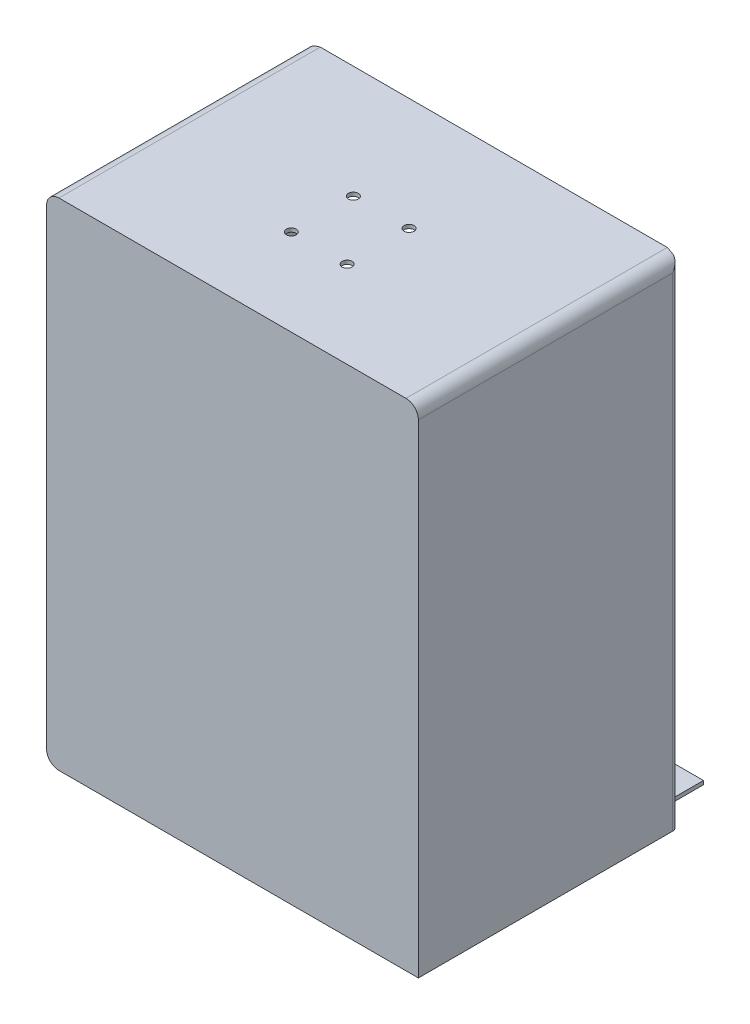
SolidWorks part; units mm, degrees
material "PPE"
ref_plane "Front Plane" through (0, 0, 0) normal (0, 0, 1) x (1, 0, 0)
ref_plane "Top Plane" through (0, 0, 0) normal (0, 1, 0) x (1, 0, 0)
ref_plane "Right Plane" through (0, 0, 0) normal (1, 0, 0) x (0, 0, -1)
sketch "Sketch2" plane through (0, 0, 0) normal (0, 0, 1) x (1, 0, 0)
  line L1 (-140, -200) -> (150, -200)
  line L2 (-150, -190) -> (-150, 190)
  line L3 (-140, 200) -> (140, 200)
  line L4 (150, -200) -> (150, 190)
  line L5 (-150, -200) -> (150, 200) construction
  line L6 (-150, 200) -> (150, -200) construction
  arc A0 (-140, -200) -> (-150, -190) centre (-140, -190) cw
  arc A1 (140, 200) -> (150, 190) centre (140, 190) cw
  arc A2 (-140, 200) -> (-150, 190) centre (-140, 190) ccw
  point P0 (0, 0)
  dimension "D3" = 10
  dimension "D1" = 400
  dimension "D2" = 300
extrude "Boss-Extrude1" add sketch "Sketch2" along normal blind 250
shell "Shell1" thickness 3 removed face at (-20.2959, 27.4387, 0)
sketch "Sketch4" plane through (0, 200, 0) normal (0, 1, 0) x (1, 0, 0)
  line L1 (140, 0) -> (-140, 0) construction
  line L3 (-150, -250) -> (-150, 0) construction
  circle A0 centre (-22.5, -130) radius 4
  circle A1 centre (22.5, -130) radius 4
  circle A2 centre (-22.5, -180) radius 4
  circle A3 centre (22.5, -180) radius 4
  dimension "D1" = 8
  dimension "D2" = 45
  dimension "D6" = 50
  dimension "D3" = 50
  dimension "D4" = 130
  dimension "D5" = 127.5
extrude "Cut-Extrude1" cut sketch "Sketch4" against normal through all
sketch "Sketch6" plane through (0, 200, 0) normal (0, 1, 0) x (1, 0, 0)
  line L0 (-140, 0) -> (-150, 0) construction
  line L1 (-130, 0) -> (-150, 0)
  line L2 (-130, 0) -> (-130, -25)
  line L3 (140, 0) -> (-140, 0) construction
  line L4 (-150, -250) -> (-150, 0) construction
  line L5 (-150, 0) -> (-150, -45.4706)
  arc A0 (-130, -25) -> (-145, -40) centre (-145, -25) cw
  arc A1 (-145, -40) -> (-150, -45) centre (-145, -45) ccw
  point P10 (-130, -40)
  point P12 (0, 0)
  line M10 (140, 0) -> (-140, 0)
  line M11 (-140, 0) -> (-140, -250)
  dimension "D3" = 15
  dimension "D2" = 5
  dimension "D1" = 40
  dimension "D4" = 25
  dimension "D5" = 45
extrude "Cut-Extrude3" cut sketch "Sketch6" against normal up to surface (400 mm away) contours A1 A0 L1 L5 M11 region at (-145.0647, 200, 20.2114) up to face at (22.5, -200, 134)
extrude "Cut-Extrude4" cut sketch "Sketch6<3>" against normal blind 414 contours A0 L2 M10 M11 region at (-135.2505, 200, 17.8024)
sketch "Sketch6<3>" plane through (0, 200, 0) normal (0, 1, 0) x (1, 0, 0) same geometry as "Sketch6"
mirror "Mirror1" about plane through (0, 0, 0) normal (1, 0, 0) of "Cut-Extrude3", "Cut-Extrude4"
sketch "Sketch7" plane through (0, 200, 0) normal (0, 1, 0) x (1, 0, 0)
  line L1 (-140, -39.1421) -> (151.0246, -39.1421)
  line L2 (-140, -39.1421) -> (-140, 9.442)
  line L3 (-140, 9.442) -> (151.0246, 9.442)
  line L4 (151.0246, -39.1421) -> (151.0246, 9.442)
extrude "Cut-Extrude5" cut sketch "Sketch7" against normal blind 232
